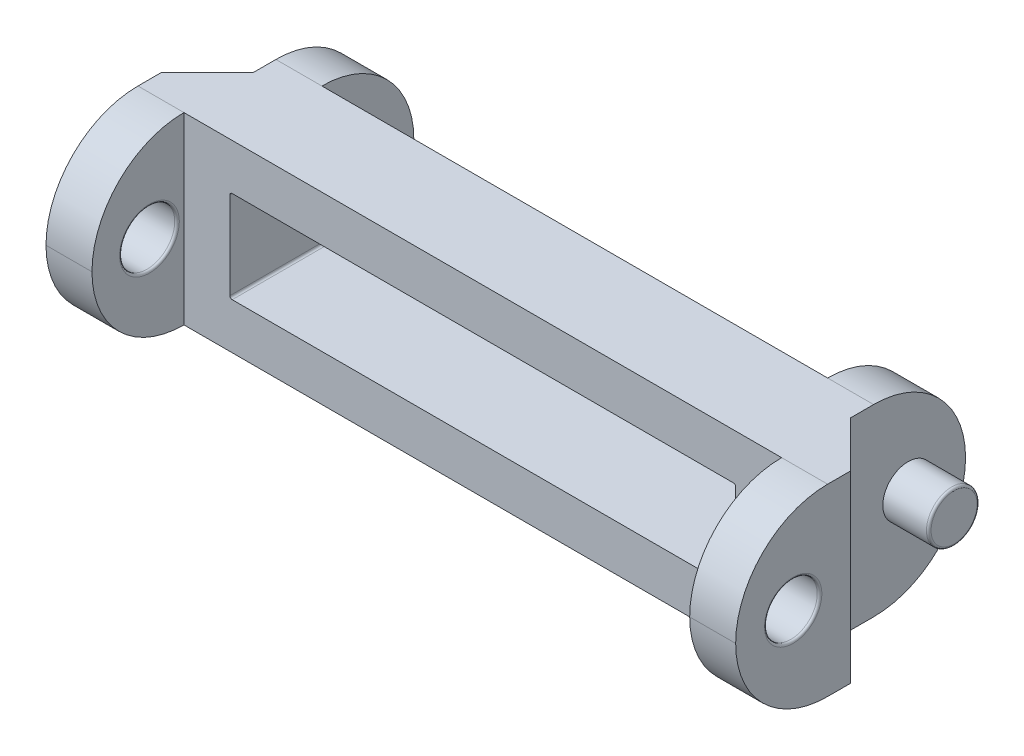
SolidWorks part; units mm, degrees
ref_plane "Front Plane" through (0, 0, 0) normal (0, 0, 1) x (1, 0, 0)
ref_plane "Top Plane" through (0, 0, 0) normal (0, 1, 0) x (1, 0, 0)
ref_plane "Right Plane" through (0, 0, 0) normal (1, 0, 0) x (0, 0, -1)
sketch "Sketch1" plane through (0, 0, 0) normal (0, 0, 1) x (1, 0, 0)
  line L2 (-5.5, -1) -> (5.5, -1)
  line L3 (-5.5, -1) -> (-5.5, 1)
  line L4 (-5.5, 1) -> (5.5, 1)
  line L5 (5.5, -1) -> (5.5, 1)
  line L6 (-5.5, -1) -> (5.5, 1) construction
  line L7 (-5.5, 1) -> (5.5, -1) construction
  point P1 (0, 0)
  dimension "D1" = 11
  dimension "D2" = 2
extrude "Extrude-Thin2" add sketch "Sketch1" along normal mid plane 2 thin thin type one direction wall 1
sketch "Sketch3" plane through (6.5, 0, 0) normal (1, 0, 0) x (0, 0, -1)
  line L0 (-1, 2) -> (1, 2) construction
  line L1 (-0.5, 2) -> (-3, 2)
  line L2 (-0.5, 2) -> (-0.5, -2)
  line L3 (-0.5, -2) -> (-3, -2)
  line L4 (-3, 2) -> (-3, -2)
  line L5 (-1, -2) -> (1, -2) construction
  dimension "D1" = 0.5
  dimension "D2" = 2.5
extrude "Boss-Extrude1" add sketch "Sketch3" along normal blind 1
fillet "Fillet1" radius 2 2 edges at (7, -2, 3) (7, 2, 3)
chamfer "Chamfer1" distance 1 angle 45 1 edges at (6.5, 0, 0.5)
mirror "Mirror2" about plane through (0, 0, 0) normal (1, 0, 0) of "Boss-Extrude1"
sketch "Sketch5" plane through (6.5, 0, 0) normal (1, 0, 0) x (0, 0, -1)
  line L0 (0.5, -2) -> (1, -2) construction
  line L1 (1, 2) -> (3, 2)
  line L2 (1, 2) -> (1, -2)
  line L3 (1, -2) -> (3, -2)
  line L4 (3, 2) -> (3, -2)
  dimension "D1" = 2
extrude "Boss-Extrude2" add sketch "Sketch5" against normal up to surface (1 mm away) up to face at (5.5, 0, 0)
fillet "Fillet2" radius 2 2 edges at (6, -2, -3) (6, 2, -3)
fillet "Fillet3" radius 2 2 edges at (-7, -2, 3) (-7, 2, 3)
sketch "Sketch6" plane through (-6.5, 0, 0) normal (-1, 0, 0) x (0, 0, 1)
  line L0 (0.5, 2) -> (-1, 2) construction
  line L1 (-1, 2) -> (-3, 2)
  line L2 (-1, 2) -> (-1, -2)
  line L3 (-1, -2) -> (-3, -2)
  line L4 (-3, 2) -> (-3, -2)
  line L5 (0.5, -2) -> (-1, -2) construction
  line L6 (-1, 2) -> (-1, -2) construction
  point P8 (-1, 2)
  dimension "D1" = 2
chamfer "Chamfer2" distance 1 angle 45 1 edges at (-6.5, 0, 0.5)
extrude "Boss-Extrude4" add sketch "Sketch6" against normal up to surface (1 mm away) up to face at (-5.5, 0, 0)
fillet "Fillet5" radius 2 2 edges at (-6, -2, -3) (-6, 2, -3)
sketch "Sketch7" plane through (7.5, 0, 0) normal (1, 0, 0) x (0, 0, -1)
  line L0 (-0.5, 0) -> (-3, 0) construction
  line L1 (-0.5, -2) -> (-0.5, 2) construction
  circle A0 centre (-1.75, 0) radius 0.5738
extrude "Cut-Extrude1" cut sketch "Sketch7" against normal blind 1
sketch "Sketch8" plane through (6.5, 0, 0) normal (1, 0, 0) x (0, 0, -1)
  line L0 (0.5, 0) -> (3, 0) construction
  line L1 (0.5, 2) -> (0.5, -2) construction
  circle A0 centre (1.75, 0) radius 0.55
extrude "Boss-Extrude5" add sketch "Sketch8" along normal blind 1
fillet "Fillet7" radius 0.05 1 edges at (7.5, 0, -2.3)
fillet "Fillet8" radius 0.05 2 edges at (5.5, 1, 0) (5.5, -1, 0)
fillet "Fillet9" radius 0.05 2 edges at (-5.5, 1, 0) (-5.5, -1, 0)
fillet "Fillet10" radius 0.05 2 edges at (6.5, 0, 1.1762) (7.5, 0, 1.1762)
sketch "Sketch9" plane through (-7.5, 0, 0) normal (-1, 0, 0) x (0, 0, 1)
  line L0 (0.5, 0) -> (3, 0) construction
  line L1 (0.5, -2) -> (0.5, 2) construction
  circle A0 centre (1.75, 0) radius 0.6
extrude "Cut-Extrude2" cut sketch "Sketch9" against normal blind 1
fillet "Fillet11" radius 0.05 2 edges at (-6.5, 0, 2.35) (-7.5, 0, 2.35)
sketch "Sketch10" plane through (-6.5, 0, 0) normal (-1, 0, 0) x (0, 0, 1)
  line L0 (-0.5, 0) -> (-3, 0) construction
  line L1 (-0.5, -2) -> (-0.5, 2) construction
  circle A0 centre (-1.75, 0) radius 0.55
  point P7 (-4.9939, -0.4874)
extrude "Boss-Extrude6" add sketch "Sketch10" along normal blind 1
fillet "Fillet12" radius 0.05 1 edges at (-7.5, 0, -1.2)
